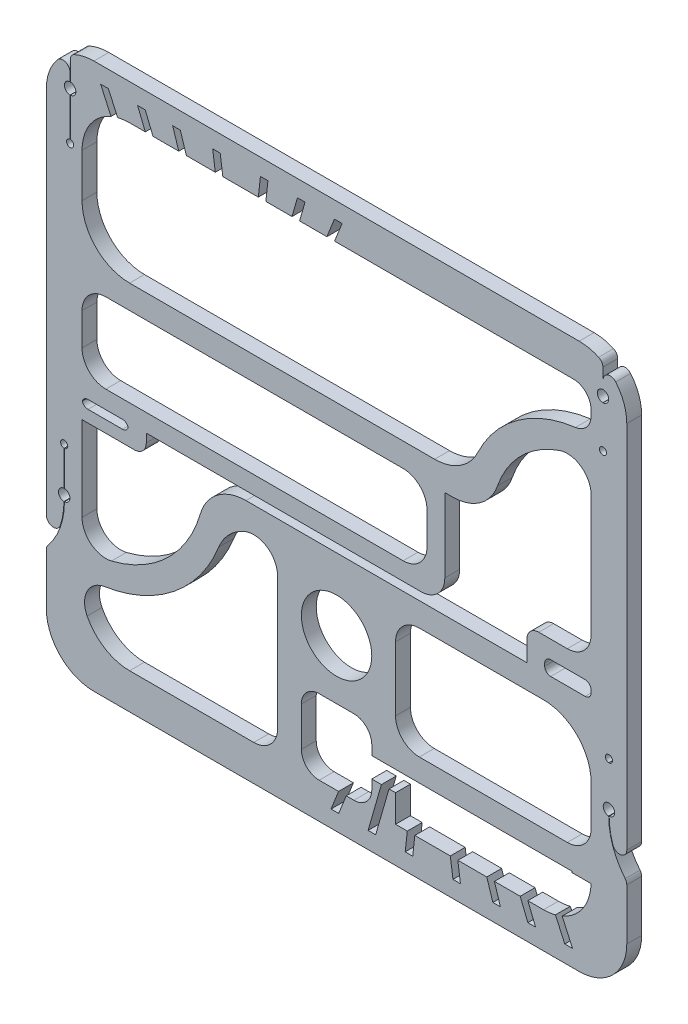
SolidWorks part; units mm, degrees
ref_plane "Front Plane" through (0, 0, 0) normal (0, 0, 1) x (1, 0, 0)
ref_plane "Top Plane" through (0, 0, 0) normal (0, 1, 0) x (1, 0, 0)
ref_plane "Right Plane" through (0, 0, 0) normal (1, 0, 0) x (0, 0, -1)
sketch "Sketch1" plane through (0, 0, 0) normal (0, 0, 1) x (1, 0, 0)
  line L0 (44.642, 21.8842) -> (44.642, 18.0742) construction
  line L1 (-10.1934, 21.8842) -> (51.7832, 21.8842)
  line L2 (-10.1934, 21.8842) -> (-10.1934, -36.406)
  line L3 (-10.1934, -36.406) -> (51.7832, -36.406)
  line L4 (51.7832, 21.8842) -> (51.7832, -36.406)
  line L5 (47.9732, -32.596) -> (-6.3834, -32.596)
  line L6 (47.9732, -32.596) -> (47.9732, 18.0742)
  line L7 (47.9732, 18.0742) -> (-6.3834, 18.0742)
  line L8 (-6.3834, -32.596) -> (-6.3834, 18.0742)
  line L9 (44.642, 19.9792) -> (-35.1587, 19.9792) construction
  line L10 (-6.3834, -31.0517) -> (-10.1934, -31.0517) construction
  line L11 (-8.2884, -31.0517) -> (-8.2884, 6.9585) construction
  line L12 (20.6521, 19.9792) -> (21.1982, 19.9792) construction
  line L14 (3.0779, -32.596) -> (3.0779, -36.406) construction
  line L15 (3.0779, -34.501) -> (37.3423, -34.501) construction
  line L16 (47.9732, -11.8991) -> (47.9732, 12.9942) construction
  line L17 (51.7832, 15.2205) -> (47.9732, 15.2205) construction
  line L18 (49.8782, 15.2205) -> (49.8782, -0.9437) construction
  line L20 (20.9378, -34.501) -> (20.3916, -34.501) construction
  line L21 (-6.3834, 8.0412) -> (-6.3834, -11.8991) construction
  dimension "D1" = 3.81
  dimension "D2" = 3.81
extrude "Boss-Extrude1" add sketch "Sketch1" along normal blind 1.5875
sketch "Sketch2" plane through (0, 0, 0) normal (0, 0, -1) x (-1, 0, 0)
  line L0 (-47.9732, -32.596) -> (-47.9732, 18.0742) construction
  line L1 (-34.8696, 3.2518) -> (6.3834, 3.2518)
  line L2 (-47.9732, 3.653) -> (-47.9732, 0.4065)
  line L3 (-37.4096, 0.7118) -> (6.3834, 0.7118)
  line L4 (6.3834, 3.2518) -> (6.3834, 0.7118)
  line L5 (6.3834, 18.0742) -> (6.3834, -32.596) construction
  line L8 (-47.9732, -13.182) -> (-9.1041, -13.182)
  line L9 (-47.9732, -13.182) -> (-47.9732, -10.642)
  line L10 (-47.9732, -10.642) -> (-6.771, -10.642)
  line L11 (1.357, -21.2563) -> (14.2432, -21.2563) construction
  line L12 (6.3834, -23.7963) -> (6.3834, -26.3363)
  line L13 (-47.9732, 13.8154) -> (-47.9732, 11.2754)
  line L14 (-41.1149, -10.642) -> (-0.4749, -10.642) construction
  line L15 (-40.2005, -1.1932) -> (-39.5655, -1.1932) construction
  arc A0 (-47.9732, 11.2754) -> (-37.4096, 0.7118) centre (-47.9732, 0.7118) cw
  arc A1 (-47.9732, 13.8154) -> (-34.8696, 3.2518) centre (-47.9732, 0.4065) cw
  arc A2 (6.3834, -23.7963) -> (-6.771, -10.642) centre (6.3834, -10.642) cw
  arc A3 (-9.1041, -13.182) -> (6.3834, -26.3363) centre (6.3834, -10.642) ccw
  circle A5 centre (1.357, -18.2591) radius 2.9972 construction
  line M5 (-47.9732, -32.596) -> (-47.9732, 18.0742)
  line M7 (6.3834, 18.0742) -> (6.3834, -32.596)
  dimension "D5" = 2.54
  dimension "D1" = 2.54
  dimension "D2" = 2.54
  dimension "D3" = 2.54
  dimension "D4" = 2.54
  dimension "D6" = 2.54
  dimension "D7" = 2.54
  dimension "D8" = 1.905
extrude "Boss-Extrude2" add sketch "Sketch2" against normal up to surface (1.5875 mm away) contours A1 A0 L3 L1 M5 M7 | L10 L8 M5 M7 region at (14.2431, 2.6927, 0) region at (-5.8176, -25.0663, 0) up to face at (20.7949, -7.2609, 1.5875)
sketch "Sketch3" plane through (0, 0, 0) normal (0, 0, -1) x (-1, 0, 0)
  line L0 (-47.9732, -7.1876) -> (-41.1149, -7.1876)
  line L1 (-47.9732, -10.642) -> (-47.9732, 11.2754) construction
  line L3 (-41.1149, -7.1876) -> (-41.1149, -10.642)
  line L4 (-47.9732, -10.642) -> (-6.771, -10.642) construction
  line L5 (-41.1149, -10.642) -> (-43.0199, -10.642)
  line L6 (-43.0199, -10.642) -> (-43.0199, -9.0926)
  line L7 (-43.0199, -9.0926) -> (-47.9732, -9.0926)
  line L8 (-47.9732, -9.0926) -> (-47.9732, -7.1876)
  line L10 (-32.3519, 0.7118) -> (-32.3519, -9.7276)
  line L11 (-37.4096, 0.7118) -> (6.3834, 0.7118) construction
  line L13 (-32.3519, -9.7276) -> (6.3834, -9.7276)
  line L14 (6.3834, 0.7118) -> (6.3834, -23.7963) construction
  line L15 (6.3834, -9.7276) -> (6.3834, -7.8226)
  line L16 (6.3834, -7.8226) -> (-30.4469, -7.8226)
  line L17 (-30.4469, -7.8226) -> (-30.4469, 0.7118)
  line L18 (-30.4469, 0.7118) -> (-32.3519, 0.7118)
  line L19 (-0.4749, -9.7276) -> (-41.1149, -9.7276) construction
  line L20 (-33.6219, -7.1876) -> (-33.6219, -9.7276) construction
  line L21 (-41.1149, -9.7276) -> (-41.1149, -10.642) construction
  dimension "D1" = 1.905
  dimension "D2" = 1.905
  dimension "D3" = 2.54
  dimension "D4" = 1.905
  dimension "D5" = 1.27
  dimension "D6" = 1.905
extrude "Boss-Extrude3" add sketch "Sketch3" against normal up to surface (1.5875 mm away) up to face at (21.3162, -5.4863, 1.5875)
fillet "Fillet1" radius 5.08 4 edges at (51.7832, -36.406, 0.7937) (-10.1934, -36.406, 0.7937) (-10.1934, 21.8842, 0.7937) (51.7832, 21.8842, 0.7937)
fillet "Fillet2" radius 5.08 9 edges at (9.1041, -13.182, 0.7937) (47.9732, -13.182, 0.7937) (47.9732, -32.596, 0.7937) (-6.3834, -32.596, 0.7937) (34.8696, 3.2518, 0.7937) (-6.3834, 3.2518, 0.7937) (-6.3834, 18.0742, 0.7937) (6.771, -10.642, 0.7937) (37.4096, 0.7118, 0.7937)
fillet "Fillet3" radius 2.54 6 edges at (47.9732, -7.1876, 0.7937) (30.4469, -7.8226, 0.7937) (32.3519, -9.7276, 0.7937) (47.9732, 11.2754, 0.7937) (-6.3834, -26.3363, 0.7937) (-6.3834, -23.7963, 0.7937)
fillet "Fillet4" radius 2.54 3 edges at (-6.3834, 0.7118, 0.7937) (30.4469, 0.7118, 0.7937) (-6.3834, -7.8226, 0.7937)
sketch "Sketch5" plane through (0, 0, 0) normal (0, 0, -1) x (-1, 0, 0)
  line L0 (-42.8932, -13.182) -> (-12.943, -13.182) construction
  line L1 (-27.0941, -13.182) -> (-14.4957, -13.182)
  line L2 (-27.0941, -13.182) -> (-27.0941, -32.596)
  line L3 (-27.0941, -32.596) -> (-14.4957, -32.596)
  line L4 (-14.4957, -13.182) -> (-14.4957, -32.596)
  line L5 (1.3034, -32.596) -> (-42.8932, -32.596) construction
  line L6 (-24.5541, -18.2972) -> (-27.0941, -18.2972) construction
  line L9 (-17.0357, -18.2972) -> (-14.4957, -18.2972) construction
  circle A1 centre (-20.7949, -18.2972) radius 3.7592 construction
  dimension "D1" = 2.54
extrude "Boss-Extrude4" add sketch "Sketch5" against normal up to surface (1.5875 mm away) up to face at (12.0318, -3.5554, 1.5875)
sketch "Sketch6" plane through (0, 0, 0) normal (0, 0, -1) x (-1, 0, 0)
  circle A0 centre (-20.7949, -18.2972) radius 3.7592 construction
  circle A1 centre (-20.7949, -18.2972) radius 3.7592
extrude "Cut-Extrude2" cut sketch "Sketch6" against normal up to surface (1.5875 mm away) up to face at (5.503, -23.566, 1.5875)
sketch "Sketch7" plane through (0, 0, 0) normal (0, 0, -1) x (-1, 0, 0)
  line L0 (-27.0941, -13.182) -> (-27.0941, -32.596) construction
  line L1 (-24.5541, -24.5964) -> (-17.0357, -24.5964)
  line L2 (-24.5541, -24.5964) -> (-24.5541, -32.596)
  line L3 (-24.5541, -32.596) -> (-17.0357, -32.596)
  line L4 (-17.0357, -24.5964) -> (-17.0357, -32.596)
  line L5 (-14.4957, -32.596) -> (-14.4957, -13.182) construction
  line L6 (1.3034, -32.596) -> (-14.4957, -32.596) construction
  line L7 (-20.7949, -22.0564) -> (-6.5424, -22.0564) construction
  line L8 (-20.7949, -22.0564) -> (-20.7949, -21.3452) construction
  circle A0 centre (-20.7949, -18.2972) radius 3.7592 construction
  dimension "D1" = 2.54
  dimension "D2" = 2.54
  dimension "D3" = 2.54
extrude "Cut-Extrude3" cut sketch "Sketch7" against normal up to surface (1.5875 mm away) up to face at (24.5541, -18.2972, 1.5875)
fillet "Fillet5" radius 1.905 4 edges at (24.5541, -32.596, 0.7937) (17.0357, -32.596, 0.7938) (17.0357, -24.5964, 0.7938) (24.5541, -24.5964, 0.7938)
sketch "Sketch8" plane through (0, 0, 0) normal (0, 0, -1) x (-1, 0, 0)
  line L0 (-47.9732, -27.516) -> (-47.9732, -18.262) construction
  line L1 (-47.9732, -25.103) -> (-27.0941, -25.103)
  line L2 (-47.9732, -25.103) -> (-47.9732, -27.643)
  line L3 (-47.9732, -27.643) -> (-27.0941, -27.643)
  line L4 (-27.0941, -25.103) -> (-27.0941, -27.643)
  line L5 (-27.0941, -13.182) -> (-27.0941, -32.596) construction
  line L6 (-45.7916, -27.643) -> (-20.3916, -27.643) construction
  dimension "D1" = 2.54
extrude "Boss-Extrude5" add sketch "Sketch8" against normal up to surface (1.5875 mm away) up to face at (20.7949, -28.5962, 1.5875)
fillet "Fillet6" radius 2.54 5 edges at (27.0941, -13.182, 0.7937) (14.4957, -13.182, 0.7937) (14.4957, -32.596, 0.7937) (27.0941, -25.103, 0.7937) (47.9732, -25.103, 0.7937)
sketch "Sketch4" plane through (0, 0, 0) normal (0, 0, -1) x (-1, 0, 0)
  line L32 (4.2018, 13.1212) -> (4.2018, 15.0262)
  line L33 (4.2018, 15.0262) -> (1.9539, 15.0262)
  line L34 (1.9539, 15.0262) -> (4.2018, 19.9792)
  line L35 (4.2018, 19.9792) -> (3.6556, 19.9792)
  line L36 (3.6556, 19.9792) -> (1.4078, 15.0262)
  line L37 (1.4078, 15.0262) -> (-1.7417, 15.0262)
  line L38 (-1.7417, 15.0262) -> (0.2648, 19.9792)
  line L39 (0.2648, 19.9792) -> (-0.2814, 19.9792)
  line L40 (-0.2814, 19.9792) -> (-2.2879, 15.0262)
  line L41 (-2.2879, 15.0262) -> (-5.0437, 15.0262)
  line L42 (-5.0437, 15.0262) -> (-3.469, 19.9792)
  line L43 (-3.469, 19.9792) -> (-4.0152, 19.9792)
  line L44 (-4.0152, 19.9792) -> (-5.5899, 15.0262)
  line L45 (-5.5899, 15.0262) -> (-8.3965, 15.0262)
  line L46 (-8.3965, 15.0262) -> (-7.7108, 19.9792)
  line L47 (-7.7108, 19.9792) -> (-8.257, 19.9792)
  line L48 (-8.257, 19.9792) -> (-8.9427, 15.0262)
  line L49 (-8.9427, 15.0262) -> (-12.2319, 15.0262)
  line L50 (-12.2319, 15.0262) -> (-12.7781, 19.9792)
  line L51 (-12.7781, 19.9792) -> (-13.3242, 19.9792)
  line L52 (-13.3242, 19.9792) -> (-12.7781, 15.0262)
  line L53 (-12.7781, 15.0262) -> (-15.2926, 15.0262)
  line L54 (-15.2926, 15.0262) -> (-16.7151, 19.9792)
  line L55 (-16.7151, 19.9792) -> (-17.2612, 19.9792)
  line L56 (-17.2612, 19.9792) -> (-15.8388, 15.0262)
  line L57 (-15.8388, 15.0262) -> (-18.6963, 15.0262)
  line L58 (-18.6963, 15.0262) -> (-20.6521, 19.9792)
  line L59 (-20.6521, 19.9792) -> (-21.1982, 19.9792)
  line L60 (-21.1982, 19.9792) -> (-19.2425, 15.0262)
  line L61 (-19.2425, 15.0262) -> (-21.1982, 15.0262)
  line L62 (-21.1982, 15.0262) -> (-21.1982, 13.1212)
  line L63 (-21.1982, 13.1212) -> (4.2018, 13.1212)
  line L64 (4.2018, 13.1212) -> (4.2018, 15.0262) construction
  line L65 (4.2018, 15.0262) -> (1.9539, 15.0262) construction
  line L66 (1.9539, 15.0262) -> (4.2018, 19.9792) construction
  line L67 (4.2018, 19.9792) -> (3.6556, 19.9792) construction
  line L68 (3.6556, 19.9792) -> (1.4078, 15.0262) construction
  line L69 (1.4078, 15.0262) -> (-1.7417, 15.0262) construction
  line L70 (-1.7417, 15.0262) -> (0.2648, 19.9792) construction
  line L71 (0.2648, 19.9792) -> (-0.2814, 19.9792) construction
  line L72 (-0.2814, 19.9792) -> (-2.2879, 15.0262) construction
  line L73 (-2.2879, 15.0262) -> (-5.0437, 15.0262) construction
  line L74 (-5.0437, 15.0262) -> (-3.469, 19.9792) construction
  line L75 (-3.469, 19.9792) -> (-4.0152, 19.9792) construction
  line L76 (-4.0152, 19.9792) -> (-5.5899, 15.0262) construction
  line L77 (-5.5899, 15.0262) -> (-8.3965, 15.0262) construction
  line L78 (-8.3965, 15.0262) -> (-7.7108, 19.9792) construction
  line L79 (-7.7108, 19.9792) -> (-8.257, 19.9792) construction
  line L80 (-8.257, 19.9792) -> (-8.9427, 15.0262) construction
  line L81 (-8.9427, 15.0262) -> (-12.2319, 15.0262) construction
  line L82 (-12.2319, 15.0262) -> (-12.7781, 19.9792) construction
  line L83 (-12.7781, 19.9792) -> (-13.3242, 19.9792) construction
  line L84 (-13.3242, 19.9792) -> (-12.7781, 15.0262) construction
  line L85 (-12.7781, 15.0262) -> (-15.2926, 15.0262) construction
  line L86 (-15.2926, 15.0262) -> (-16.7151, 19.9792) construction
  line L87 (-16.7151, 19.9792) -> (-17.2612, 19.9792) construction
  line L88 (-17.2612, 19.9792) -> (-15.8388, 15.0262) construction
  line L89 (-15.8388, 15.0262) -> (-18.6963, 15.0262) construction
  line L90 (-18.6963, 15.0262) -> (-20.6521, 19.9792) construction
  line L91 (-20.6521, 19.9792) -> (-21.1982, 19.9792) construction
  line L92 (-21.1982, 19.9792) -> (-19.2425, 15.0262) construction
  line L93 (-19.2425, 15.0262) -> (-21.1982, 15.0262) construction
  line L94 (-21.1982, 15.0262) -> (-21.1982, 13.1212) construction
  line L95 (-21.1982, 13.1212) -> (4.2018, 13.1212) construction
  line L96 (-45.7916, -27.643) -> (-45.7916, -29.548)
  line L97 (-45.7916, -29.548) -> (-43.5438, -29.548)
  line L98 (-43.5438, -29.548) -> (-45.7916, -34.501)
  line L99 (-45.7916, -34.501) -> (-45.2455, -34.501)
  line L100 (-45.2455, -34.501) -> (-42.9976, -29.548)
  line L101 (-42.9976, -29.548) -> (-39.8482, -29.548)
  line L102 (-39.8482, -29.548) -> (-41.8546, -34.501)
  line L103 (-41.8546, -34.501) -> (-41.3085, -34.501)
  line L104 (-41.3085, -34.501) -> (-39.302, -29.548)
  line L105 (-39.302, -29.548) -> (-36.5462, -29.548)
  line L106 (-36.5462, -29.548) -> (-38.1208, -34.501)
  line L107 (-38.1208, -34.501) -> (-37.5747, -34.501)
  line L108 (-37.5747, -34.501) -> (-36, -29.548)
  line L109 (-36, -29.548) -> (-33.1934, -29.548)
  line L110 (-33.1934, -29.548) -> (-33.879, -34.501)
  line L111 (-33.879, -34.501) -> (-33.3329, -34.501)
  line L112 (-33.3329, -34.501) -> (-32.6472, -29.548)
  line L113 (-32.6472, -29.548) -> (-29.358, -29.548)
  line L114 (-29.358, -29.548) -> (-28.8118, -34.501)
  line L115 (-28.8118, -34.501) -> (-28.2656, -34.501)
  line L116 (-28.2656, -34.501) -> (-28.8118, -29.548)
  line L117 (-28.8118, -29.548) -> (-26.2973, -29.548)
  line L118 (-26.2973, -29.548) -> (-24.8748, -34.501)
  line L119 (-24.8748, -34.501) -> (-24.3286, -34.501)
  line L120 (-24.3286, -34.501) -> (-25.7511, -29.548)
  line L121 (-25.7511, -29.548) -> (-22.8935, -29.548)
  line L122 (-22.8935, -29.548) -> (-20.9378, -34.501)
  line L123 (-20.9378, -34.501) -> (-20.3916, -34.501)
  line L124 (-20.3916, -34.501) -> (-22.3474, -29.548)
  line L125 (-22.3474, -29.548) -> (-20.3916, -29.548)
  line L126 (-20.3916, -29.548) -> (-20.3916, -27.643)
  line L127 (-20.3916, -27.643) -> (-45.7916, -27.643)
  line L128 (-45.7916, -27.643) -> (-45.7916, -29.548) construction
  line L129 (-45.7916, -29.548) -> (-43.5438, -29.548) construction
  line L130 (-43.5438, -29.548) -> (-45.7916, -34.501) construction
  line L131 (-45.7916, -34.501) -> (-45.2455, -34.501) construction
  line L132 (-45.2455, -34.501) -> (-42.9976, -29.548) construction
  line L133 (-42.9976, -29.548) -> (-39.8482, -29.548) construction
  line L134 (-39.8482, -29.548) -> (-41.8546, -34.501) construction
  line L135 (-41.8546, -34.501) -> (-41.3085, -34.501) construction
  line L136 (-41.3085, -34.501) -> (-39.302, -29.548) construction
  line L137 (-39.302, -29.548) -> (-36.5462, -29.548) construction
  line L138 (-36.5462, -29.548) -> (-38.1208, -34.501) construction
  line L139 (-38.1208, -34.501) -> (-37.5747, -34.501) construction
  line L140 (-37.5747, -34.501) -> (-36, -29.548) construction
  line L141 (-36, -29.548) -> (-33.1934, -29.548) construction
  line L142 (-33.1934, -29.548) -> (-33.879, -34.501) construction
  line L143 (-33.879, -34.501) -> (-33.3329, -34.501) construction
  line L144 (-33.3329, -34.501) -> (-32.6472, -29.548) construction
  line L145 (-32.6472, -29.548) -> (-29.358, -29.548) construction
  line L146 (-29.358, -29.548) -> (-28.8118, -34.501) construction
  line L147 (-28.8118, -34.501) -> (-28.2656, -34.501) construction
  line L148 (-28.2656, -34.501) -> (-28.8118, -29.548) construction
  line L149 (-28.8118, -29.548) -> (-26.2973, -29.548) construction
  line L150 (-26.2973, -29.548) -> (-24.8748, -34.501) construction
  line L151 (-24.8748, -34.501) -> (-24.3286, -34.501) construction
  line L152 (-24.3286, -34.501) -> (-25.7511, -29.548) construction
  line L153 (-25.7511, -29.548) -> (-22.8935, -29.548) construction
  line L154 (-22.8935, -29.548) -> (-20.9378, -34.501) construction
  line L155 (-20.9378, -34.501) -> (-20.3916, -34.501) construction
  line L156 (-20.3916, -34.501) -> (-22.3474, -29.548) construction
  line L157 (-22.3474, -29.548) -> (-20.3916, -29.548) construction
  line L158 (-20.3916, -29.548) -> (-20.3916, -27.643) construction
  line L159 (-20.3916, -27.643) -> (-45.7916, -27.643) construction
  line L263 (4.3288, 12.9942) -> (4.3288, 15.1532)
  line L264 (4.3288, 15.1532) -> (2.151, 15.1532)
  line L265 (2.151, 15.1532) -> (4.3989, 20.1062)
  line L266 (4.3989, 20.1062) -> (3.5738, 20.1062)
  line L267 (3.5738, 20.1062) -> (1.3259, 15.1532)
  line L268 (1.3259, 15.1532) -> (-1.5532, 15.1532)
  line L269 (-1.5532, 15.1532) -> (0.4532, 20.1062)
  line L270 (0.4532, 20.1062) -> (-0.367, 20.1062)
  line L271 (-0.367, 20.1062) -> (-2.3735, 15.1532)
  line L272 (-2.3735, 15.1532) -> (-4.8701, 15.1532)
  line L273 (-4.8701, 15.1532) -> (-3.2954, 20.1062)
  line L274 (-3.2954, 20.1062) -> (-4.1081, 20.1062)
  line L275 (-4.1081, 20.1062) -> (-5.6828, 15.1532)
  line L276 (-5.6828, 15.1532) -> (-8.2507, 15.1532)
  line L277 (-8.2507, 15.1532) -> (-7.565, 20.1062)
  line L278 (-7.565, 20.1062) -> (-8.3676, 20.1062)
  line L279 (-8.3676, 20.1062) -> (-9.0533, 15.1532)
  line L280 (-9.0533, 15.1532) -> (-12.1181, 15.1532)
  line L281 (-12.1181, 15.1532) -> (-12.6643, 20.1062)
  line L282 (-12.6643, 20.1062) -> (-13.466, 20.1062)
  line L283 (-13.466, 20.1062) -> (-12.9198, 15.1532)
  line L284 (-12.9198, 15.1532) -> (-15.1969, 15.1532)
  line L285 (-15.1969, 15.1532) -> (-16.6194, 20.1062)
  line L286 (-16.6194, 20.1062) -> (-17.4298, 20.1062)
  line L287 (-17.4298, 20.1062) -> (-16.0074, 15.1532)
  line L288 (-16.0074, 15.1532) -> (-18.6099, 15.1532)
  line L289 (-18.6099, 15.1532) -> (-20.5657, 20.1062)
  line L290 (-20.5657, 20.1062) -> (-21.3849, 20.1062)
  line L291 (-21.3849, 20.1062) -> (-19.4292, 15.1532)
  line L292 (-19.4292, 15.1532) -> (-21.3252, 15.1532)
  line L293 (-21.3252, 15.1532) -> (-21.3252, 12.9942)
  line L294 (-21.3252, 12.9942) -> (4.3288, 12.9942)
  line L295 (-45.9186, -27.516) -> (-45.9186, -29.675)
  line L296 (-45.9186, -29.675) -> (-43.7409, -29.675)
  line L297 (-43.7409, -29.675) -> (-45.9887, -34.628)
  line L298 (-45.9887, -34.628) -> (-45.1636, -34.628)
  line L299 (-45.1636, -34.628) -> (-42.9158, -29.675)
  line L300 (-42.9158, -29.675) -> (-40.0367, -29.675)
  line L301 (-40.0367, -29.675) -> (-42.0431, -34.628)
  line L302 (-42.0431, -34.628) -> (-41.2229, -34.628)
  line L303 (-41.2229, -34.628) -> (-39.2164, -29.675)
  line L304 (-39.2164, -29.675) -> (-36.7198, -29.675)
  line L305 (-36.7198, -29.675) -> (-38.2945, -34.628)
  line L306 (-38.2945, -34.628) -> (-37.4818, -34.628)
  line L307 (-37.4818, -34.628) -> (-35.9071, -29.675)
  line L308 (-35.9071, -29.675) -> (-33.3392, -29.675)
  line L309 (-33.3392, -29.675) -> (-34.0248, -34.628)
  line L310 (-34.0248, -34.628) -> (-33.2222, -34.628)
  line L311 (-33.2222, -34.628) -> (-32.5366, -29.675)
  line L312 (-32.5366, -29.675) -> (-29.4717, -29.675)
  line L313 (-29.4717, -29.675) -> (-28.9256, -34.628)
  line L314 (-28.9256, -34.628) -> (-28.1239, -34.628)
  line L315 (-28.1239, -34.628) -> (-28.67, -29.675)
  line L316 (-28.67, -29.675) -> (-26.3929, -29.675)
  line L317 (-26.3929, -29.675) -> (-24.9705, -34.628)
  line L318 (-24.9705, -34.628) -> (-24.16, -34.628)
  line L319 (-24.16, -34.628) -> (-25.5825, -29.675)
  line L320 (-25.5825, -29.675) -> (-22.9799, -29.675)
  line L321 (-22.9799, -29.675) -> (-21.0242, -34.628)
  line L322 (-21.0242, -34.628) -> (-20.205, -34.628)
  line L323 (-20.205, -34.628) -> (-22.1607, -29.675)
  line L324 (-22.1607, -29.675) -> (-20.2646, -29.675)
  line L325 (-20.2646, -29.675) -> (-20.2646, -27.516)
  line L326 (-20.2646, -27.516) -> (-45.9186, -27.516)
  dimension "D1" = 0
  dimension "D2" = 0
  dimension "D3" = 0.127
  dimension "D4" = 0.127
extrude "Cut-Extrude1" cut sketch "Sketch4" against normal up to surface (1.5875 mm away) up to face at (37.2819, -19.3942, 1.5875)
sketch "Sketch9" plane through (0, 0, 0) normal (0, 0, -1) x (-1, 0, 0)
  circle A0 centre (-49.2432, 18.0742) radius 0.6096 construction
  circle A1 centre (7.6534, 18.0742) radius 0.6096 construction
  circle A2 centre (8.2884, -19.8366) radius 0.6096 construction
  circle A3 centre (-49.8782, -19.8366) radius 0.6096 construction
  circle A4 centre (-49.2432, 18.0742) radius 0.6096
  circle A5 centre (7.6534, 18.0742) radius 0.6096
  circle A6 centre (8.2884, -19.8366) radius 0.6096
  circle A7 centre (-49.8782, -19.8366) radius 0.6096
extrude "Cut-Extrude4" cut sketch "Sketch9" against normal up to surface (1.5875 mm away) up to face at (31.4097, -31.792, 1.5875)
sketch "Sketch10" plane through (0, 0, 1.5875) normal (0, 0, 1) x (1, 0, 0)
  line L0 (-7.6407, 18.6837) -> (-7.6407, 20.7449) construction
  line L1 (-7.6407, 13.375) -> (-7.6407, 17.4647) construction
  line L2 (-7.6661, 17.4647) -> (-7.6661, 13.375) construction
  line L3 (-7.6661, 19.5715) -> (-7.6661, 18.6837) construction
  line L4 (-7.6407, 18.6837) -> (-7.6407, 20.7449)
  line L5 (-7.6407, 13.375) -> (-7.6407, 17.4647)
  line L6 (-7.6661, 17.4647) -> (-7.6661, 13.375)
  line L7 (-7.6661, 19.5715) -> (-7.6661, 18.6837)
  line L8 (49.2305, 18.6837) -> (49.2305, 20.7449) construction
  line L9 (49.2305, 13.375) -> (49.2305, 17.4647) construction
  line L10 (49.2559, 17.4647) -> (49.2559, 13.375) construction
  line L11 (49.2559, 19.5715) -> (49.2559, 18.6837) construction
  line L12 (49.2305, 18.6837) -> (49.2305, 20.7449)
  line L13 (49.2305, 13.375) -> (49.2305, 17.4647)
  line L14 (49.2559, 17.4647) -> (49.2559, 13.375)
  line L15 (49.2559, 19.5715) -> (49.2559, 18.6837)
  line L16 (49.8909, -15.5181) -> (49.8909, -19.2271) construction
  line L17 (49.8655, -15.5181) -> (49.8655, -19.2271) construction
  line L18 (49.8909, -15.5181) -> (49.8909, -19.2271)
  line L19 (49.8655, -15.5181) -> (49.8655, -19.2271)
  line L20 (-8.2757, -15.5181) -> (-8.2757, -19.2271) construction
  line L21 (-8.3011, -15.5181) -> (-8.3011, -19.2271) construction
  line L22 (-8.2757, -15.5181) -> (-8.2757, -19.2271)
  line L23 (-8.3011, -15.5181) -> (-8.3011, -19.2271)
  line L24 (51.7832, -31.326) -> (51.7832, 16.8042) construction
  line L25 (51.7832, -25.8445) -> (51.7832, -22.639)
  line L26 (-10.1934, 16.8042) -> (-10.1934, -31.326) construction
  line L27 (-10.1934, -22.639) -> (-10.1934, -25.8445)
  arc A1 (-7.1902, 21.4403) -> (-7.6407, 20.7449) centre (-6.8787, 20.7449) ccw construction
  arc A2 (-7.6661, 13.375) -> (-7.6407, 13.375) centre (-7.6534, 12.9942) ccw construction
  arc A3 (-7.6661, 19.5715) -> (-9.013, 20.0598) centre (-8.4281, 19.5715) ccw construction
  arc A4 (-5.1134, 21.8842) -> (-10.1934, 16.8042) centre (-5.1134, 16.8042) ccw construction
  arc A5 (-7.1902, 21.4403) -> (-7.6407, 20.7449) centre (-6.8787, 20.7449) ccw
  arc A6 (-7.6661, 13.375) -> (-7.6407, 13.375) centre (-7.6534, 12.9942) ccw
  arc A7 (-7.6661, 19.5715) -> (-9.013, 20.0598) centre (-8.4281, 19.5715) ccw
  arc A8 (-7.1902, 21.4403) -> (-9.013, 20.0598) centre (-5.1134, 16.8042) ccw
  circle A9 centre (-7.6534, 18.0742) radius 0.6096 construction
  arc A10 (-7.6407, 18.6837) -> (-7.6661, 18.6837) centre (-7.6534, 18.0742) ccw
  arc A11 (-7.6661, 17.4647) -> (-7.6407, 17.4647) centre (-7.6534, 18.0742) ccw
  arc A12 (49.2305, 20.7449) -> (48.7801, 21.4403) centre (48.4685, 20.7449) ccw construction
  arc A13 (49.2305, 13.375) -> (49.2559, 13.375) centre (49.2432, 12.9942) ccw construction
  arc A14 (50.6029, 20.0598) -> (49.2559, 19.5715) centre (50.0179, 19.5715) ccw construction
  arc A15 (49.2305, 20.7449) -> (48.7801, 21.4403) centre (48.4685, 20.7449) ccw
  arc A16 (49.2305, 13.375) -> (49.2559, 13.375) centre (49.2432, 12.9942) ccw
  arc A17 (50.6029, 20.0598) -> (49.2559, 19.5715) centre (50.0179, 19.5715) ccw
  arc A18 (49.8909, -15.5181) -> (49.8655, -15.5181) centre (49.8782, -15.1373) ccw construction
  arc A19 (49.9036, -20.4457) -> (50.2983, -22.8798) centre (57.6041, -20.4462) ccw construction
  arc A20 (49.8528, -20.4457) -> (51.6105, -25.3613) centre (57.6041, -20.4462) ccw construction
  arc A21 (50.2983, -22.8798) -> (51.7832, -22.639) centre (51.0212, -22.639) ccw construction
  arc A22 (51.7832, -25.8445) -> (51.6105, -25.3613) centre (51.0212, -25.8445) ccw construction
  arc A23 (49.8909, -15.5181) -> (49.8655, -15.5181) centre (49.8782, -15.1373) ccw
  arc A24 (49.9036, -20.4457) -> (50.2983, -22.8798) centre (57.6041, -20.4462) ccw
  arc A25 (49.8528, -20.4457) -> (51.6105, -25.3613) centre (57.6041, -20.4462) ccw
  arc A26 (50.2983, -22.8798) -> (51.7832, -22.639) centre (51.0212, -22.639) ccw
  arc A27 (51.7832, -25.8445) -> (51.6105, -25.3613) centre (51.0212, -25.8445) ccw
  arc A28 (-10.1934, -22.639) -> (-8.7084, -22.8798) centre (-9.4314, -22.639) ccw construction
  arc A29 (-10.0206, -25.3613) -> (-8.263, -20.4457) centre (-16.0142, -20.4462) ccw construction
  arc A30 (-8.7084, -22.8798) -> (-8.3138, -20.4457) centre (-16.0142, -20.4462) ccw construction
  arc A31 (-8.2757, -15.5181) -> (-8.3011, -15.5181) centre (-8.2884, -15.1373) ccw construction
  arc A32 (-10.1934, -22.639) -> (-8.7084, -22.8798) centre (-9.4314, -22.639) ccw
  arc A33 (-10.0206, -25.3613) -> (-8.263, -20.4457) centre (-16.0142, -20.4462) ccw
  arc A34 (-8.7084, -22.8798) -> (-8.3138, -20.4457) centre (-16.0142, -20.4462) ccw
  arc A35 (-8.2757, -15.5181) -> (-8.3011, -15.5181) centre (-8.2884, -15.1373) ccw
  arc A36 (51.7832, 16.8042) -> (46.7032, 21.8842) centre (46.7032, 16.8042) ccw construction
  arc A37 (50.6029, 20.0598) -> (48.7801, 21.4403) centre (46.7032, 16.8042) ccw
  circle A38 centre (49.2432, 18.0742) radius 0.6096 construction
  arc A39 (49.2559, 18.6837) -> (49.2305, 18.6837) centre (49.2432, 18.0742) ccw
  arc A40 (49.2305, 17.4647) -> (49.2559, 17.4647) centre (49.2432, 18.0742) ccw
  circle A41 centre (49.8782, -19.8366) radius 0.6096 construction
  arc A42 (49.8909, -19.2271) -> (49.8655, -19.2271) centre (49.8782, -19.8366) ccw
  arc A43 (49.8528, -20.4457) -> (49.9036, -20.4457) centre (49.8782, -19.8366) ccw
  circle A44 centre (-8.2884, -19.8366) radius 0.6096 construction
  arc A45 (-8.2757, -19.2271) -> (-8.3011, -19.2271) centre (-8.2884, -19.8366) ccw
  arc A46 (-8.3138, -20.4457) -> (-8.263, -20.4457) centre (-8.2884, -19.8366) ccw
  arc A47 (-10.0206, -25.3613) -> (-10.1934, -25.8445) centre (-9.4314, -25.8445) ccw construction
  arc A48 (-10.0206, -25.3613) -> (-10.1934, -25.8445) centre (-9.4314, -25.8445) ccw
extrude "Slots for carbon" cut sketch "Sketch10" against normal through all
fillet "Fillet7" radius 1.905 2 edges at (47.9732, 13.8154, 0.7937) (47.9732, 18.0742, 0.7937)
sketch "Sketch11" plane through (0, 0, 0) normal (0, 0, -1) x (-1, 0, 0)
  line L0 (-0.4749, -9.7276) -> (-0.4749, -11.912)
  line L1 (-29.8119, -9.7276) -> (6.3834, -9.7276) construction
  line L2 (-0.4749, -11.912) -> (6.3834, -11.912)
  line L3 (6.3834, -9.7276) -> (6.3834, -20.9479) construction
  line L4 (6.3834, -11.912) -> (6.3834, -10.642)
  line L5 (6.3834, -10.642) -> (1.4301, -10.642)
  line L6 (1.4301, -10.642) -> (1.4301, -9.7276)
  line L7 (1.4301, -9.7276) -> (-0.4749, -9.7276)
  line L11 (-0.4749, -9.7276) -> (-0.4749, -10.642) construction
  line L12 (-41.1149, -10.642) -> (-0.4749, -10.642) construction
  dimension "D1" = 1.27
  dimension "D2" = 1.905
  dimension "D3" = 1.27
extrude "Boss-Extrude6" add sketch "Sketch11" against normal up to surface (1.5875 mm away) up to face at (20.7949, -2.3483, 1.5875)
fillet "Fillet8" radius 1.27 2 edges at (41.1149, -7.1876, 0.7937) (0.4749, -11.912, 0.7938)
fillet "Fillet9" radius 0.635 8 edges at (47.9732, -10.642, 0.7937) (47.9732, -9.0926, 0.7937) (43.0199, -9.0926, 0.7937) (43.0199, -10.642, 0.7937) (-1.4301, -10.642, 0.7938) (-1.4301, -9.7276, 0.7937) (-6.3834, -10.642, 0.7938) (-6.3834, -9.7276, 0.7937)
